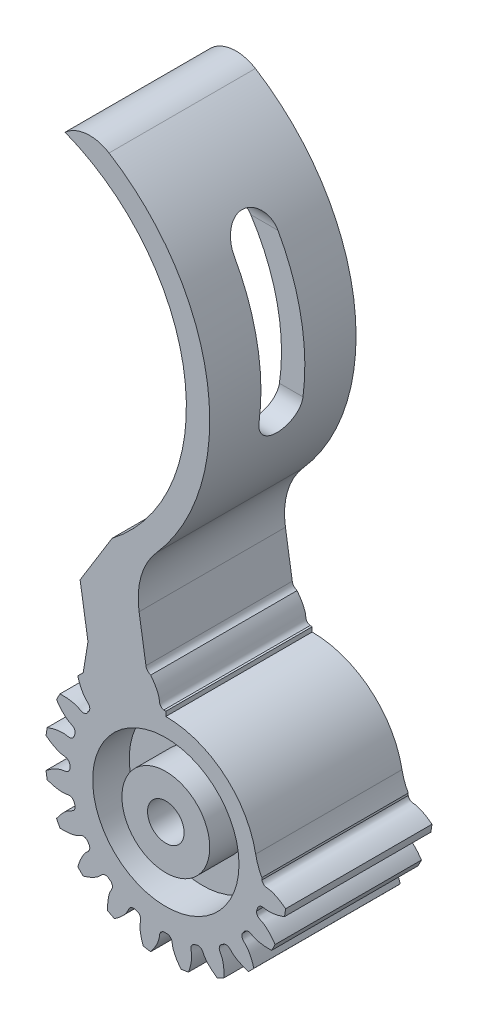
SolidWorks part; units mm, degrees
material "聚脂树脂"
ref_plane "前视基准面" through (0, 0, 0) normal (0, 0, 1) x (1, 0, 0)
ref_plane "上视基准面" through (0, 0, 0) normal (0, 1, 0) x (1, 0, 0)
ref_plane "右视基准面" through (0, 0, 0) normal (1, 0, 0) x (0, 0, -1)
other "Configuration Table"
sketch "草图1" plane through (0, 0, 0) normal (0, 0, 1) x (1, 0, 0)
  circle A0 centre (0, 0) radius 16.5
extrude "凸台-拉伸1" add sketch "草图1" along normal blind 20
ref_axis "基准轴1" through (0, 0, -1.5) along (0, 0, 1)
sketch "草图2" plane through (0, 0, 0) normal (0, 0, 1) x (1, 0, 0)
  line L0 (0, 0) -> (0, 16.5) construction
  circle A0 centre (0, 0) radius 16.5 construction
  arc A1 (0.29, 13.1218) -> (-0.29, 13.1218) centre (0, 0) ccw
  arc A2 (4.7717, 18.7474) -> (-4.7717, 18.7474) centre (0, 0) ccw
  spline S0 degree 3 poles (0.29, 13.1218) (0.9168, 13.3402) (0.8356, 13.7807) (0.9193, 14.205) (0.9283, 14.2463) (0.9395, 14.293) (0.9529, 14.3448) (0.969, 14.4018) (0.9878, 14.4638) (1.0095, 14.5309) (1.0345, 14.6028) (1.0629, 14.6795) (1.0948, 14.7608) (1.1305, 14.8467) (1.1702, 14.9371) (1.2141, 15.0317) (1.2623, 15.1305) (1.315, 15.2334) (1.3725, 15.3401) (1.4349, 15.4506) (1.5023, 15.5646) (1.575, 15.6821) (1.653, 15.8029) (1.7366, 15.9267) (1.826, 16.0534) (1.9211, 16.1829) (2.0223, 16.3149) (2.1296, 16.4493) (2.2432, 16.5859) (2.3632, 16.7244) (2.4897, 16.8646) (2.6229, 17.0065) (2.7628, 17.1496) (2.9095, 17.2939) (3.0632, 17.4391) (3.224, 17.585) (3.3918, 17.7313) (3.567, 17.8779) (3.7493, 18.0245) (3.9391, 18.1709) (4.1363, 18.3167) (4.4122, 18.5125) (4.6259, 18.6545) (4.7717, 18.7474) knots 0 0 0 0 0.165916 0.170906 0.176664 0.183189 0.190482 0.198542 0.207371 0.216967 0.22733 0.238462 0.250361 0.263027 0.276462 0.290664 0.305634 0.321371 0.337876 0.355149 0.37319 0.391998 0.411574 0.431917 0.453028 0.474907 0.497554 0.520968 0.54515 0.570099 0.595817 0.622302 0.649554 0.677575 0.706363 0.735918 0.766242 0.797333 0.829191 0.861818 0.895212 0.929373 1 1 1 1
  spline S1 degree 3 poles (-0.29, 13.1218) (-0.9168, 13.3402) (-0.8356, 13.7807) (-0.9193, 14.205) (-0.9283, 14.2463) (-0.9395, 14.293) (-0.9529, 14.3448) (-0.969, 14.4018) (-0.9878, 14.4638) (-1.0095, 14.5309) (-1.0345, 14.6028) (-1.0629, 14.6795) (-1.0948, 14.7608) (-1.1305, 14.8467) (-1.1702, 14.9371) (-1.2141, 15.0317) (-1.2623, 15.1305) (-1.315, 15.2334) (-1.3725, 15.3401) (-1.4349, 15.4506) (-1.5023, 15.5646) (-1.575, 15.6821) (-1.653, 15.8029) (-1.7366, 15.9267) (-1.826, 16.0534) (-1.9211, 16.1829) (-2.0223, 16.3149) (-2.1296, 16.4493) (-2.2432, 16.5859) (-2.3632, 16.7244) (-2.4897, 16.8646) (-2.6229, 17.0065) (-2.7628, 17.1496) (-2.9095, 17.2939) (-3.0632, 17.4391) (-3.224, 17.585) (-3.3918, 17.7313) (-3.567, 17.8779) (-3.7493, 18.0245) (-3.9391, 18.1709) (-4.1363, 18.3167) (-4.4122, 18.5125) (-4.6259, 18.6545) (-4.7717, 18.7474) knots 0 0 0 0 0.165916 0.170906 0.176664 0.183189 0.190482 0.198542 0.207371 0.216967 0.22733 0.238462 0.250361 0.263027 0.276462 0.290664 0.305634 0.321371 0.337876 0.355149 0.37319 0.391998 0.411574 0.431917 0.453028 0.474907 0.497554 0.520968 0.54515 0.570099 0.595817 0.622302 0.649554 0.677575 0.706363 0.735918 0.766242 0.797333 0.829191 0.861818 0.895212 0.929373 1 1 1 1
extrude "切除-拉伸1" cut sketch "草图2" along normal through all
pattern_circular "阵列(圆周)1" count 20 over 360 about axis through (0, 0, -1.5) along (0, 0, 1) of "切除-拉伸1"
sketch "草图3" plane through (0, 0, 0) normal (0, 0, 1) x (1, 0, 0)
  circle A0 centre (0, 0) radius 15 construction
  dimension "Dn" = 30
sketch "草图4" plane through (0, 0, 20) normal (0, 0, 1) x (1, 0, 0)
  line L0 (0, 0) -> (0, 24.252) construction
  line L1 (0, 0) -> (-4.1504, 26.2048) construction
  line L2 (-14.6667, -3.2847) -> (-22.6322, 47.0071) construction
  line L3 (-12.3599, 26.8976) -> (-7.9015, -1.2515)
  line L4 (-4.4584, 28.1491) -> (0, 0)
  line L5 (-15.1584, 78.5964) -> (-13.768, 74.7667)
  line L6 (-11.294, 12.029) -> (-10.6385, 16.029)
  line L7 (-3.0932, 16.2075) -> (-2.5812, 16.2969)
  line L8 (0, 0) -> (-34.8237, -5.5155) construction
  line L9 (-7.9015, -1.2515) -> (0, 0)
  circle A0 centre (0, 0) radius 12.5 construction
  circle A1 centre (-23.1908, 50.5343) radius 29.189 construction
  arc A2 (-2.0665, 16.3701) -> (-3.0932, 16.2075) centre (0, 0) ccw construction
  arc A3 (-4.4584, 28.1491) -> (-15.1584, 78.5964) centre (-23.1908, 50.5343) ccw
  circle A4 centre (-23.1908, 50.5343) radius 26 construction
  arc A6 (-12.3599, 26.8976) -> (-13.768, 74.7667) centre (-23.1908, 50.5343) ccw
  arc A8 (-3.7791, 12.5692) -> (-4.3306, 12.39) centre (0, 0) ccw construction
  arc A9 (-7.024, 14.9303) -> (-7.9502, 14.4584) centre (0, 0) ccw construction
  arc A10 (-7.4782, 10.7862) -> (-7.9474, 10.4453) centre (0, 0) ccw construction
  arc A12 (-3.7791, 12.5692) -> (-4.3306, 12.39) centre (0, 0) ccw
  arc A13 (-7.024, 14.9303) -> (-7.9502, 14.4584) centre (0, 0) ccw
  arc A14 (-7.4782, 10.7862) -> (-7.9474, 10.4453) centre (0, 0) ccw
  spline S0 degree 3 poles (2295.3671, 1929.7263) (-117.6975, -134.774) (-40.8912, 20.8175) (-11.0168, 11.9483) (-10.7713, 11.8675) (-10.4966, 11.7648) (-10.2471, 11.6599) (-10.0224, 11.5547) (-9.822, 11.4509) (-9.671, 11.3649) (-9.5386, 11.2841) (-9.4441, 11.2225) (-9.3578, 11.1623) (-9.3008, 11.1209) (-9.2491, 11.0817) (-9.2026, 11.0451) (-9.1503, 11.0021) (-9.105, 10.9626) (-4.5559, 6.7443) (-24.7562, -23.4769) (1867.2073, 2351.7135) knots -12.160638 -12.160638 -12.160638 -12.160638 0.502446 0.525093 0.568083 0.608002 0.644851 0.678629 0.709336 0.736973 0.749639 0.77267 0.783033 0.792629 0.801458 0.809518 0.816811 0.829094 0.834084 3.350793 3.350793 3.350793 3.350793 only from (-11.294, 12.029) to (-7.9474, 10.4453) construction
  spline S1 degree 3 poles (-3000.2151, -128.3054) (33.5455, 6.2288) (-2.7783, 7.6499) (-3.5171, 13.8097) (-3.5224, 13.8696) (-3.5265, 13.9372) (-3.5289, 13.9963) (-3.5307, 14.0865) (-3.5293, 14.2134) (-3.5206, 14.3824) (-3.5033, 14.5733) (-3.4754, 14.7858) (-3.4352, 15.0192) (-3.381, 15.2729) (-3.3111, 15.5461) (-3.2398, 15.7847) (-3.1737, 15.9845) (7.1936, 45.3178) (178.2143, 16.0013) (-2910.3372, -722.7198) knots -2.350827 -2.350827 -2.350827 -2.350827 0.165916 0.170906 0.183189 0.190482 0.198542 0.207371 0.22733 0.250361 0.276462 0.305634 0.337876 0.37319 0.411574 0.453028 0.474907 0.497554 13.160601 13.160601 13.160601 13.160601 only from (-3.7791, 12.5692) to (-3.0932, 16.2075) construction
  spline S2 degree 3 poles (2779.3421, 1125.9713) (-153.5845, -91.8071) (-32.4569, 32.4347) (-6.7853, 14.7679) (-6.5768, 14.6152) (-6.3474, 14.4326) (-6.1425, 14.2557) (-5.9612, 14.0862) (-5.8028, 13.9257) (-5.6857, 13.7971) (-5.5848, 13.6794) (-5.514, 13.5916) (-5.4504, 13.5077) (-5.409, 13.4507) (-5.3719, 13.3975) (-5.3391, 13.3482) (-5.3027, 13.2912) (-5.2717, 13.2396) (-2.2488, 7.822) (-30.7993, -14.6778) (2502.5391, 1659.6136) knots -12.160638 -12.160638 -12.160638 -12.160638 0.502446 0.525093 0.568083 0.608002 0.644851 0.678629 0.709336 0.736973 0.749639 0.77267 0.783033 0.792629 0.801458 0.809518 0.816811 0.829094 0.834084 3.350793 3.350793 3.350793 3.350793 only from (-7.024, 14.9303) to (-4.3306, 12.39) construction
  spline S3 degree 3 poles (-2813.7256, -1049.1431) (29.9789, 16.29) (-5.0063, 6.4169) (-7.6124, 12.047) (-7.636, 12.1023) (-7.6607, 12.1653) (-7.6812, 12.2208) (-7.7108, 12.3061) (-7.7487, 12.4272) (-7.7927, 12.5905) (-7.8352, 12.7775) (-7.8743, 12.9882) (-7.9082, 13.2226) (-7.9351, 13.4806) (-7.9531, 13.762) (-7.959, 14.011) (-7.9578, 14.2215) (-7.1625, 45.3227) (164.5472, 70.2894) (-2544.5625, -1586.6911) knots -2.350827 -2.350827 -2.350827 -2.350827 0.165916 0.170906 0.183189 0.190482 0.198542 0.207371 0.22733 0.250361 0.276462 0.305634 0.337876 0.37319 0.411574 0.453028 0.474907 0.497554 13.160601 13.160601 13.160601 13.160601 only from (-7.4782, 10.7862) to (-7.9502, 14.4584) construction
  spline S4 degree 3 poles (-3.7791, 12.5692) (-3.2504, 12.9706) (-3.4637, 13.3644) (-3.5171, 13.8097) (-3.5224, 13.8696) (-3.5265, 13.9372) (-3.5289, 13.9963) (-3.5307, 14.0865) (-3.5293, 14.2134) (-3.5206, 14.3824) (-3.5033, 14.5733) (-3.4754, 14.7858) (-3.4352, 15.0192) (-3.381, 15.2729) (-3.3111, 15.5461) (-3.224, 15.8378) (-3.1479, 16.0599) (-3.1017, 16.1848) (-3.0932, 16.2075) knots 0 0 0 0 0.165916 0.170906 0.183189 0.190482 0.198542 0.207371 0.22733 0.250361 0.276462 0.305634 0.337876 0.37319 0.411574 0.453028 0.497554 0.507432 0.507432 0.507432 0.507432
  spline S5 degree 3 poles (-7.024, 14.9303) (-6.9129, 14.8568) (-6.7202, 14.7228) (-6.459, 14.5233) (-6.2419, 14.3433) (-6.0489, 14.1699) (-5.8792, 14.0047) (-5.7318, 13.8492) (-5.6234, 13.7255) (-5.5309, 13.613) (-5.4664, 13.5298) (-5.409, 13.4507) (-5.3719, 13.3975) (-5.3391, 13.3482) (-5.3027, 13.2912) (-5.2717, 13.2396) (-5.0532, 12.848) (-4.9943, 12.404) (-4.3306, 12.39) knots 0.492568 0.492568 0.492568 0.492568 0.546972 0.588426 0.62681 0.662124 0.694366 0.723538 0.749639 0.761538 0.783033 0.792629 0.801458 0.809518 0.816811 0.829094 0.834084 1 1 1 1
  spline S6 degree 3 poles (-7.4782, 10.7862) (-7.0995, 11.3313) (-7.424, 11.64) (-7.6124, 12.047) (-7.636, 12.1023) (-7.6607, 12.1653) (-7.6812, 12.2208) (-7.7108, 12.3061) (-7.7487, 12.4272) (-7.7927, 12.5905) (-7.8352, 12.7775) (-7.8743, 12.9882) (-7.9082, 13.2226) (-7.9351, 13.4806) (-7.9531, 13.762) (-7.9603, 14.0664) (-7.9566, 14.3011) (-7.9513, 14.4342) (-7.9502, 14.4584) knots 0 0 0 0 0.165916 0.170906 0.183189 0.190482 0.198542 0.207371 0.22733 0.250361 0.276462 0.305634 0.337876 0.37319 0.411574 0.453028 0.497554 0.507432 0.507432 0.507432 0.507432
  spline S7 degree 3 poles (-11.294, 12.029) (-11.1656, 11.9934) (-10.9409, 11.9255) (-10.6308, 11.8165) (-10.3687, 11.7125) (-10.1316, 11.6072) (-9.9192, 11.5025) (-9.7309, 11.4002) (-9.5896, 11.316) (-9.4669, 11.2376) (-9.3798, 11.1783) (-9.3008, 11.1209) (-9.2491, 11.0817) (-9.2026, 11.0451) (-9.1503, 11.0021) (-9.105, 10.9626) (-8.7761, 10.6576) (-8.5829, 10.2536) (-7.9474, 10.4453) knots 0.492568 0.492568 0.492568 0.492568 0.546972 0.588426 0.62681 0.662124 0.694366 0.723538 0.749639 0.761538 0.783033 0.792629 0.801458 0.809518 0.816811 0.829094 0.834084 1 1 1 1
  dimension "D6" = 52
  dimension "D7" = 76
  dimension "D5" = 28.5
  dimension "D10" = 25
  dimension "D9" = 80
  dimension "D1" = 9
  dimension "D2" = 15
  dimension "D3" = 8
  dimension "D4" = 28.5
  dimension "D8" = 4
extrude "凸台-拉伸2" add sketch "草图4" against normal blind 20 contours S7 A14 S6 A13 S5 A12 S4 L7 A6 | S7 region at (3.5117, 51.3198, 20) region at (-10.6183, 13.2048, 20)
fillet "圆角1" radius 1 1 edges
fillet "圆角2" radius 5 1 edges at (-15.1584, 78.5964, 10)
fillet "圆角4" radius 10 1 edges at (-4.4584, 28.1491, 10)
sketch "草图5" plane through (0, 0, 20) normal (0, 0, 1) x (1, 0, 0)
  circle A0 centre (0, 0) radius 2.5
  dimension "D1" = 5
extrude "切除-拉伸2" cut sketch "草图5" against normal blind 20
chamfer "倒角1" distance 5 angle 45 1 edges at (-12.3599, 26.8976, 10) first distance on face at (-11.4992, 21.4633, 10)
sketch "草图7" plane through (0, 0, 0) normal (0, 0, -1) x (-1, 0, 0)
  circle A0 centre (0, 0) radius 10
  dimension "D1" = 20
extrude "切除-拉伸3" cut sketch "草图7" against normal blind 3
sketch "草图8" plane through (0, 0, 20) normal (0, 0, 1) x (1, 0, 0)
  circle A0 centre (0, 0) radius 6
  circle A1 centre (0, 0) radius 10
  dimension "D1" = 12
  dimension "D2" = 20
extrude "切除-拉伸4" cut sketch "草图8" against normal blind 5
sketch "草图9" plane through (0, 0, 0) normal (1, 0, 0) x (0, 0, -1)
  line L0 (-10, 46.7) -> (-10, 64.7) construction
  line L5 (-13, 46.7) -> (-13, 64.7)
  line L6 (-7, 46.7) -> (-7, 64.7)
  line L7 (0, 31.2457) -> (0, 75.3118) construction
  arc A0 (-13, 46.7) -> (-7, 46.7) centre (-10, 46.7) ccw
  arc A1 (-7, 64.7) -> (-13, 64.7) centre (-10, 64.7) ccw
  point P2 (-10, 55.7)
  dimension "D2" = 3
  dimension "D1" = 18
  dimension "D3" = 10
  dimension "D4" = 55.7
extrude "切除-拉伸5" cut sketch "草图9" along normal blind 10 and the other way blind 10
sketch "草图10" plane through (0, 0, 0) normal (0, 0, -1) x (-1, 0, 0)
  line L0 (0, 0) -> (-26.7646, 0) construction
  line L1 (-12.5, 0) -> (-20.4748, 0)
  line L2 (-20.4748, 0) -> (-20.4748, 20.7867)
  line L3 (-20.4748, 20.7867) -> (0, 20.7867)
  line L4 (0, 20.7867) -> (0, 12.5)
  circle A0 centre (0, 0) radius 12.5
  dimension "D1" = 25
extrude "切除-拉伸6" cut sketch "草图10" against normal blind 25 contours A0 L4 L3 L2 L1 region at (12.2358, 12.4549, 0)
fillet "圆角5" radius 8 1 edges at (12.5, 0, 10)
